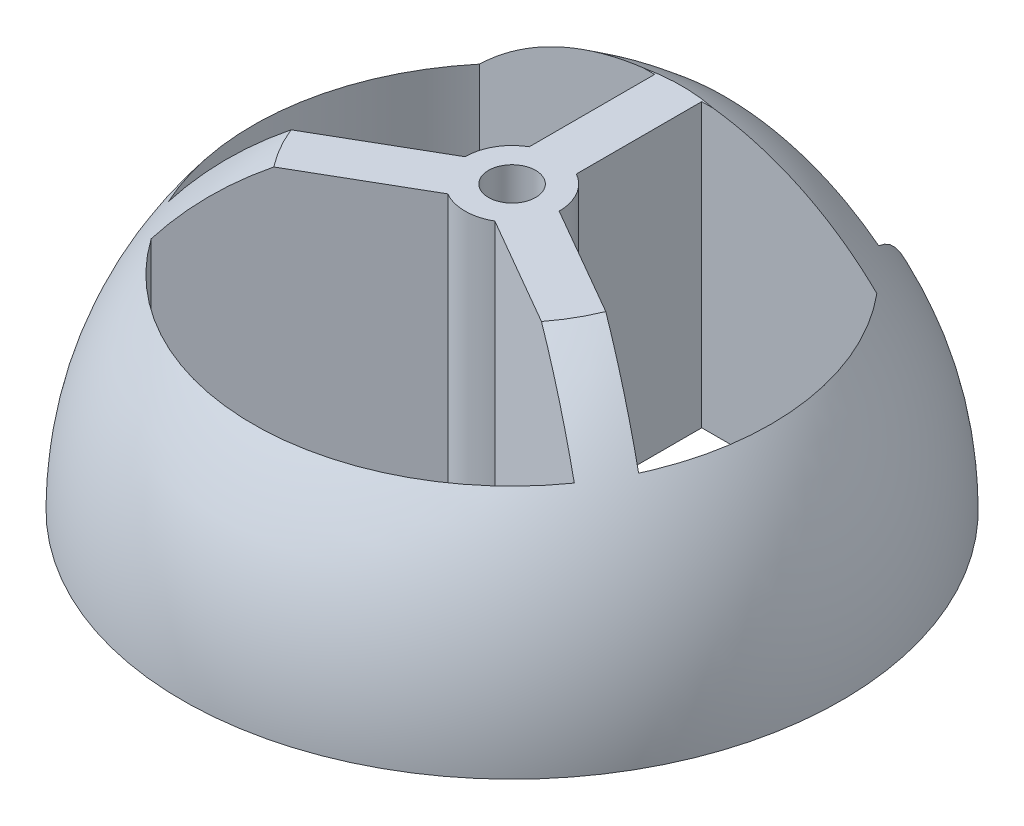
SolidWorks part; units mm, degrees
ref_plane "Front Plane" through (0, 0, 0) normal (0, 0, 1) x (1, 0, 0)
ref_plane "Top Plane" through (0, 0, 0) normal (0, 1, 0) x (1, 0, 0)
ref_plane "Right Plane" through (0, 0, 0) normal (1, 0, 0) x (0, 0, -1)
sketch "Sketch1" plane through (0, 0, 0) normal (0, 0, 1) x (1, 0, 0)
  line L0 (-754.6294, 0) -> (36976.8412, 0) construction
  line L1 (0, -754.6294) -> (0, 36976.8412) construction
  line L2 (0, 14) -> (0, 0)
  line L3 (0, 0) -> (14, 0)
  arc A0 (0, 14) -> (14, 0) centre (0, 0) cw
  dimension "D1" = 14
revolve "Revolve1" add sketch "Sketch1" angle 360 about L1
sketch "Sketch4" plane through (0, 0, 0) normal (0, 1, 0) x (1, 0, 0)
  circle A0 centre (0, 0) radius 11
  circle A1 centre (0, 0) radius 14 construction
  dimension "D1" = 3
extrude "Cut-Extrude4" cut sketch "Sketch4" along normal through all
sketch "Sketch6" plane through (0, 0, 0) normal (0, 1, 0) x (1, 0, 0)
  line L0 (-999.1642, 9.0564) -> (49000.8358, 9.0564) construction
  line L1 (-1006.7099, 13.4164) -> (48993.2901, 13.4164) construction
  line L2 (-6.5172, 9.0564) -> (6.5172, 9.0564)
  line L3 (6.5172, 9.0564) -> (4, 13.4164)
  line L5 (-4, 13.4164) -> (-6.5172, 9.0564)
  line L6 (0, -1000) -> (0, 49000) construction
  arc A0 (-4, 13.4164) -> (4, 13.4164) centre (0, 0) cw
  circle A1 centre (0, 0) radius 14 construction
  point P15 (0, 0)
  point P16 (0, 0)
  dimension "D1" = 4.36
  dimension "D2" = 60
  dimension "D3" = 8
extrude "Cut-Extrude5" cut sketch "Sketch6" along normal through all
sketch "Sketch5" plane through (0, 0, 0) normal (0, 1, 0) x (1, 0, 0)
  line L6 (-1000, 0) -> (49000, 0) construction
  line L7 (-8.4384, 7.0564) -> (-1, 7.0564)
  line L8 (8.4384, 7.0564) -> (1, 7.0564)
  line L9 (-8.4384, 9.0564) -> (-8.4384, 7.0564)
  line L10 (-8.4384, 9.0564) -> (8.4384, 9.0564)
  line L11 (8.4384, 7.0564) -> (8.4384, 9.0564)
  line L12 (-6.2435, 9.0564) -> (-6.5172, 9.0564) construction
  line L14 (0, -1000) -> (0, 49000) construction
  line L15 (-1, 7.0564) -> (-1, 1.7321)
  line L16 (1, 7.0564) -> (1, 1.7321)
  line L17 (-12.5934, -6.1161) -> (-11.5934, -7.8481)
  line L18 (-11.5934, -7.8481) -> (-1, -1.7321)
  line L19 (-12.5934, -6.1161) -> (-2, 0)
  line L20 (1, -1.7321) -> (11.5934, -7.8481)
  line L21 (11.5934, -7.8481) -> (12.5934, -6.1161)
  line L22 (12.5934, -6.1161) -> (2, 0)
  circle A2 centre (0, 0) radius 1
  circle A3 centre (0, 0) radius 11 construction
  circle A5 centre (0, 0) radius 14 construction
  arc A6 (1, 1.7321) -> (2, 0) centre (0, 0) cw
  arc A7 (1, -1.7321) -> (-1, -1.7321) centre (0, 0) cw
  arc A8 (-2, 0) -> (-1, 1.7321) centre (0, 0) cw
  dimension "D3" = 2
  dimension "D4" = 60
  dimension "D2" = 2
  dimension "D1" = 2
  dimension "D5" = 2
  dimension "D6" = 2
extrude "Boss-Extrude1" add sketch "Sketch5" along normal up to surface up to face at (0, 5.9367, -2.9334)
sketch "Sketch7" plane through (0, 0, 0) normal (0, 0, 1) x (1, 0, 0)
  line L0 (-14, 0) -> (14, 0) construction
  line L1 (-9.9793, 12) -> (10.734, 12)
  line L2 (-9.9793, 12) -> (-9.9793, 15.3753)
  line L3 (-9.9793, 15.3753) -> (10.734, 15.3753)
  line L4 (10.734, 12) -> (10.734, 15.3753)
  dimension "D1" = 12
extrude "Cut-Extrude6" cut sketch "Sketch7" against normal through all and the other way through all
